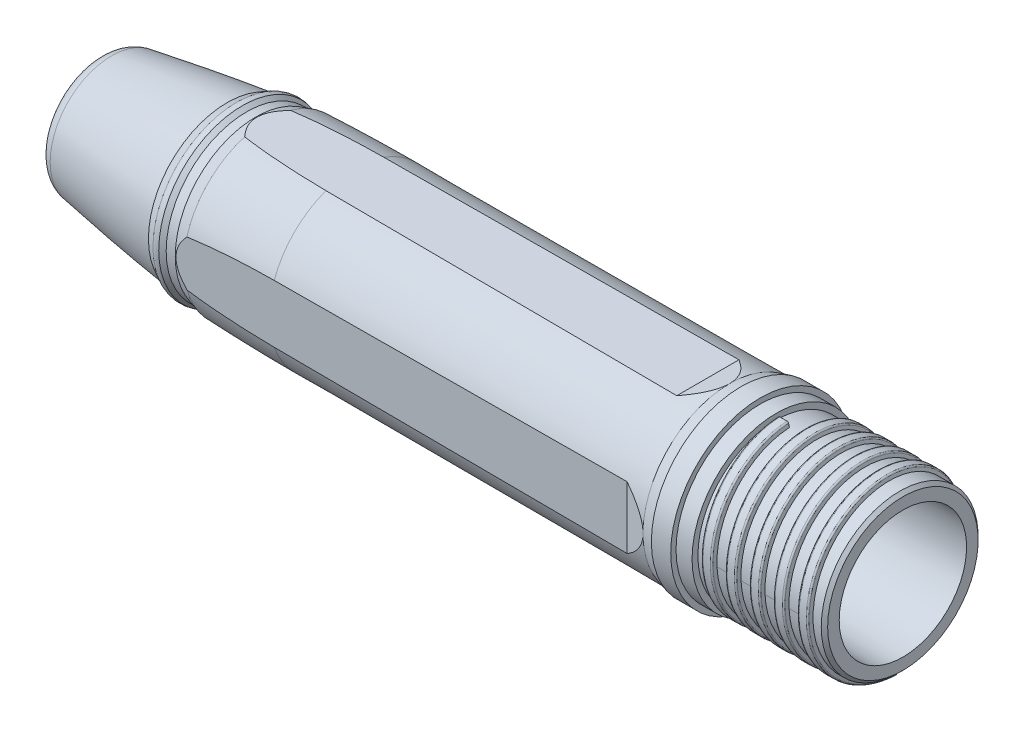
SolidWorks part; units mm, degrees
ref_plane "Plano frontal" through (0, 0, 0) normal (0, 0, 1) x (1, 0, 0)
ref_plane "Plano superior" through (0, 0, 0) normal (0, 1, 0) x (1, 0, 0)
ref_plane "Plano direito" through (0, 0, 0) normal (1, 0, 0) x (0, 0, -1)
sketch "Esboço1" plane through (0, 0, 0) normal (0, 0, 1) x (1, 0, 0)
  line L18 (0, 0) -> (65.2888, 0) construction
  line L19 (11.2816, 3.3501) -> (17.8813, 3.75)
  line L20 (60.0697, 3.9776) -> (17.8813, 3.75)
  line L21 (60.0697, 3.9776) -> (60.0697, 4.9)
  line L22 (52.1661, 4.9) -> (60.0697, 4.9)
  line L23 (11.2816, 2.815) -> (11.2816, 3.3501)
  line L24 (9.9675, 2.815) -> (11.2816, 2.815)
  line L25 (9.9675, 2.815) -> (9.9675, 3.3786)
  line L26 (18.4544, 5.221) -> (17.8639, 4.9137)
  line L27 (18.4544, 5.221) -> (18.814, 5.221) construction
  line L28 (18.814, 5.221) -> (19.0818, 5.0234)
  line L29 (19.6477, 5.0234) -> (19.0818, 5.0234)
  line L30 (20.3965, 5.2426) -> (19.6477, 5.0234)
  line L31 (49.2481, 5.4067) -> (25.8471, 5.3565)
  line L32 (49.9573, 5.5968) -> (49.2481, 5.4067)
  line L33 (49.9573, 5.5968) -> (51.1661, 5.5968)
  line L34 (51.1661, 5.5968) -> (51.1661, 5.265)
  line L35 (51.1661, 5.265) -> (52.1661, 5.265)
  line L36 (52.1661, 4.9) -> (52.1661, 5.265)
  arc A3 (10.6506, 3.8378) -> (9.9675, 3.3786) centre (10.8175, 2.8518) ccw
  arc A4 (17.8639, 4.9137) -> (10.6506, 3.8378) centre (41.7703, -180.084) ccw
  arc A5 (25.8471, 5.3565) -> (20.3965, 5.2426) centre (26.1589, -139.9763) ccw
  arc A6 (18.4544, 5.221) -> (18.814, 5.221) centre (18.6342, 4.7171) cw
revolve "Revolução1" add sketch "Esboço1" angle 360 about L18
sketch "Esboço2" plane through (0, 0, 0) normal (0, 0, 1) x (1, 0, 0)
  line L0 (20.3965, 5.2426) -> (49.2481, 5.2426) construction
  line L1 (49.2481, 5.4067) -> (49.2481, -5.4067) construction
  line L2 (49.2481, 5.4067) -> (49.2481, 7.208)
  line L3 (49.2481, 7.208) -> (19.6554, 7.208)
  line L4 (19.6554, 7.208) -> (19.6554, 5.2426)
  line L5 (19.6554, 5.2426) -> (20.3965, 5.2426) construction
  line L6 (19.6554, 5.0426) -> (20.3965, 5.0426)
  line L7 (20.3965, 5.0426) -> (47.889, 5.0426)
  line L8 (19.6554, 5.0426) -> (20.3965, 5.0426) construction
  line L9 (19.6554, 5.2426) -> (19.6554, 5.0426)
  line L11 (49.2481, 5.4067) -> (47.889, 5.0426)
  line L12 (49.9573, 5.5968) -> (49.2481, 5.4067) construction
  line L14 (20.3965, 5.0426) -> (49.2481, 5.0426) construction
  dimension "D1" = 0.2
extrude "Corte-extrusão1" cut sketch "Esboço2" against normal mid plane 10
pattern_circular "PadrãoCircular1" count 4 over 360 about axis through (52.1661, 0, 0) along (-1, 0, 0) of "Corte-extrusão1"
sketch "Esboço3" plane through (0, 0, 0) normal (0, 0, 1) x (1, 0, 0)
  line L18 (0, 0) -> (60.0697, 0) construction
  line L19 (60.0697, -4.9) -> (60.0697, 4.9) construction
  line L20 (58.2369, 4.9) -> (58.2054, 4.7674)
  line L21 (58.2054, 4.7674) -> (59.0303, 4.7674)
  line L22 (59.0303, 4.7674) -> (58.9869, 4.9)
  line L40 (58.9344, 5.0958) -> (58.9869, 4.9)
  line L41 (58.8378, 5.17) -> (58.386, 5.17)
  line L42 (58.2894, 5.0958) -> (58.2369, 4.9)
  arc A8 (58.9344, 5.0958) -> (58.8378, 5.17) centre (58.8378, 5.07) ccw
  arc A9 (58.386, 5.17) -> (58.2894, 5.0958) centre (58.386, 5.07) ccw
sketch "Esboço4" plane through (60.0697, 0, 0) normal (1, 0, 0) x (0, 0, -1)
  circle A0 centre (0, 0) radius 4.9
  circle A1 centre (0, 0) radius 4.9 construction
curve "Hélice/Espiral1" pitch 1.5 height 7.125 radius 4.9 centre (60.0697, 0, 0) axis (-1, 0, 0) start towards (0, 0, -1)
sweep "Varredura1" add profiles "Esboço3" path "Hélice/Espiral1"
sketch "Esboço5" plane through (0, 0, 0) normal (0, 0, 1) x (1, 0, 0)
  line L0 (59.2931, 0.9732) -> (58.774, -5.6205)
  line L1 (59.2931, 0.9732) -> (61.1576, 0.9732)
  line L3 (58.774, -5.6205) -> (61.1576, -5.6205)
  line L4 (61.1576, 0.9732) -> (61.1576, -5.6205)
extrude "Corte-extrusão2" cut sketch "Esboço5" against normal blind 10
combine bodies "Combinar1" operation type add bodies to combine 106 103
chamfer "Chanfro1" distance 0.2 angle 45 1 edges at (60.0697, 0, 4.9)
